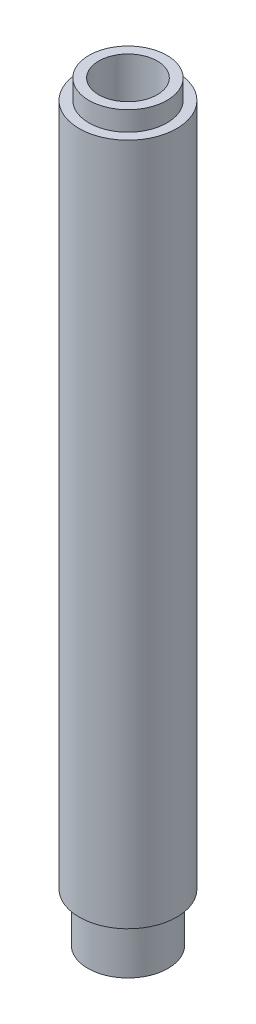
SolidWorks part; units mm, degrees
ref_plane "Front Plane" through (0, 0, 0) normal (0, 0, 1) x (1, 0, 0)
ref_plane "Top Plane" through (0, 0, 0) normal (0, 1, 0) x (1, 0, 0)
ref_plane "Right Plane" through (0, 0, 0) normal (1, 0, 0) x (0, 0, -1)
sketch "Sketch1" plane through (0, 0, 0) normal (0, 1, 0) x (1, 0, 0)
  circle A0 centre (0, 0) radius 12.7
  dimension "D1" = 25.4
extrude "Boss-Extrude1" add sketch "Sketch1" along normal blind 177.8
sketch "Sketch4" plane through (0, 177.8, 0) normal (0, 1, 0) x (1, 0, 0)
  circle A2 centre (0, 0) radius 10.16
  circle A3 centre (0, 0) radius 10.16
  dimension "D1" = 2.54
extrude "Boss-Extrude2" add sketch "Sketch4" along normal blind 5.08
sketch "Sketch5" plane through (0, 182.88, 0) normal (0, 1, 0) x (1, 0, 0)
  circle A0 centre (0, 0) radius 10.16 construction
  circle A1 centre (0, 0) radius 10.16 construction
  circle A2 centre (0, 0) radius 7.62
  dimension "D1" = 2.54
extrude "Cut-Extrude1" cut sketch "Sketch5" against normal through all
sketch "Sketch6" plane through (0, 0, 0) normal (0, -1, 0) x (1, 0, 0)
  circle A0 centre (0, 0) radius 10.4394
  circle A1 centre (0, 0) radius 7.62 construction
  circle A2 centre (0, 0) radius 7.62
  dimension "D1" = 20.8788
extrude "Boss-Extrude3" add sketch "Sketch6" along normal blind 12.7
sketch "Sketch7" plane through (0, -12.7, 0) normal (0, -1, 0) x (1, 0, 0)
  circle A0 centre (0, 0) radius 12.7 construction
  circle A1 centre (0, 0) radius 12.7
